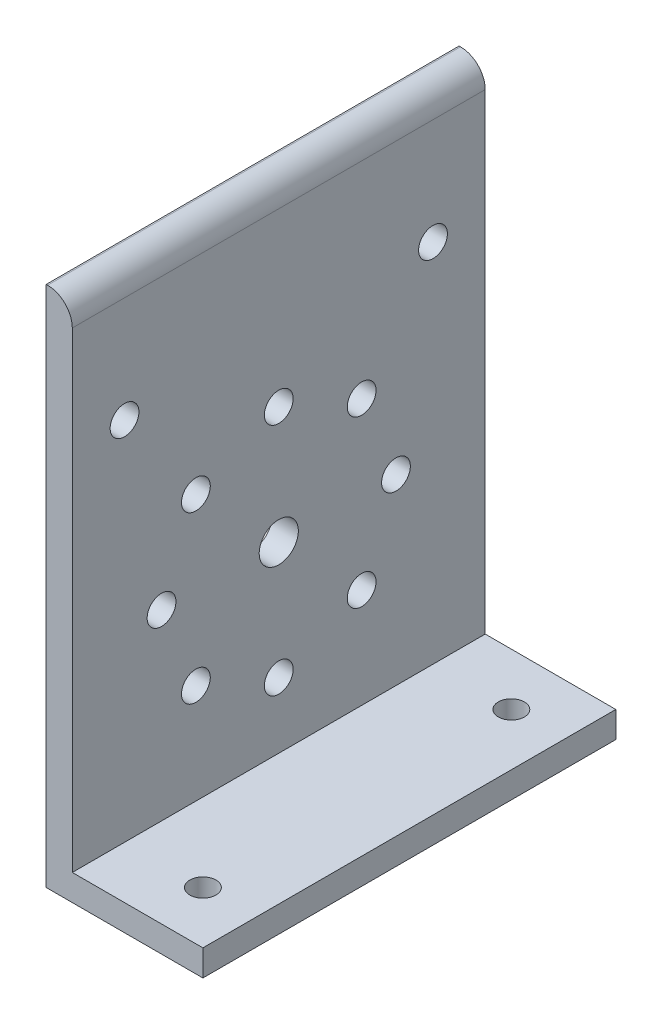
SolidWorks part; units mm, degrees
ref_plane "Front Plane" through (0, 0, 0) normal (0, 0, 1) x (1, 0, 0)
ref_plane "Top Plane" through (0, 0, 0) normal (0, 1, 0) x (1, 0, 0)
ref_plane "Right Plane" through (0, 0, 0) normal (1, 0, 0) x (0, 0, -1)
sketch "Sketch1" plane through (0, 0, 0) normal (0, 0, 1) x (1, 0, 0)
  line L2 (0, 0) -> (0, 127)
  line L3 (0, 127) -> (0.35, 127)
  line L4 (6.35, 37.75) -> (6.35, 121)
  line L6 (0, 0) -> (0, 6.35)
  line L8 (38.1, 0) -> (38.1, 0.35)
  line L9 (6.35, 6.35) -> (6.35, 37.75)
  line L11 (32.1, 6.35) -> (38.1, 6.35)
  line L12 (38.1, 6.35) -> (38.1, 0.35)
  line L13 (38.1, 0) -> (0, 0)
  line L14 (6.35, 6.35) -> (32.1, 6.35)
  arc A1 (0.35, 127) -> (6.35, 121) centre (0.35, 121) cw
  point P10 (38.1, 6.35)
  point P13 (6.35, 127)
  dimension "D1" = 127
  dimension "D2" = 38.1
  dimension "D3" = 6.35
  dimension "D4" = 6.35
extrude "Boss-Extrude1" add sketch "Sketch1" along normal blind 100.4 contours L4 A1 L3 L2 L8 region at (1.3259, 3.175, 0)
sketch "Sketch2" plane through (0, 0, 0) normal (-1, 0, 0) x (0, 0, 1)
  line L0 (50.2, 127) -> (50.2, 0)
  line L3 (100.4, 50.8) -> (0, 50.8) construction
  line L4 (100.4, 0) -> (100.4, 127) construction
  line L5 (0, 0) -> (0, 127) construction
  line L6 (100.4, 0) -> (0, 0) construction
  line L7 (100.4, 127) -> (0, 127) construction
  circle A0 centre (50.2, 50.8) radius 28.5 construction
  circle A9 centre (50.2, 50.8) radius 4.7625
  circle A10 centre (50.2, 79.3) radius 3.5
  circle A18 centre (70.3525, 70.9525) radius 3.5
  circle A19 centre (78.7, 50.8) radius 3.5
  circle A20 centre (70.3525, 30.6475) radius 3.5
  circle A21 centre (50.2, 22.3) radius 3.5
  circle A22 centre (30.0475, 30.6475) radius 3.5
  circle A23 centre (21.7, 50.8) radius 3.5
  circle A24 centre (30.0475, 70.9525) radius 3.5
  dimension "D1" = 57
  dimension "D2" = 8
  dimension "D4" = 9.525
  dimension "D3" = 50.8
extrude "Cut-Extrude1" cut sketch "Sketch2" against normal through all contours A18 | A10 | A24 | A23 | A22 | A21 | A20 | A19 | A9 region at (0, 70.9525, 70.3525)
sketch "Sketch3" plane through (0, 6.35, 0) normal (0, 1, 0) x (1, 0, 0)
  line L0 (25.4, -100.4) -> (25.4, 0) construction
  line L4 (6.35, -100.4) -> (38.1, -100.4) construction
  line L5 (6.35, 0) -> (38.1, 0) construction
  line L6 (0, -100.4) -> (0, 0) construction
  circle A0 centre (25.4, -12.7) radius 3.175
  circle A2 centre (25.4, -87.7) radius 3.175
  point P10 (0, 0)
  dimension "D2" = 6.35
  dimension "D3" = 12.7
  dimension "D4" = 12.7
  dimension "D5" = 6.35
  dimension "D1" = 25.4
extrude "Cut-Extrude2" cut sketch "Sketch3" against normal through all
ref_plane "Width Centerline Plane" through (0, 0, 50.2) normal (0, 0, 1) x (1, 0, 0)
sketch "Sketch5" plane through (6.35, 0, 0) normal (1, 0, 0) x (0, 0, -1)
  line L0 (-50.2, 6.35) -> (-50.2, 121) construction
  line L1 (-100.4, 121) -> (0, 121) construction
  line L2 (-100.4, 6.35) -> (0, 6.35) construction
  line L3 (-100.4, 6.35) -> (-100.4, 121) construction
  circle A0 centre (-87.7, 95.25) radius 3.5
  circle A2 centre (-12.7, 95.25) radius 3.5
  dimension "D1" = 7
  dimension "D2" = 25.75
  dimension "D3" = 12.7
extrude "Cut-Extrude4" cut sketch "Sketch5" against normal blind 10
